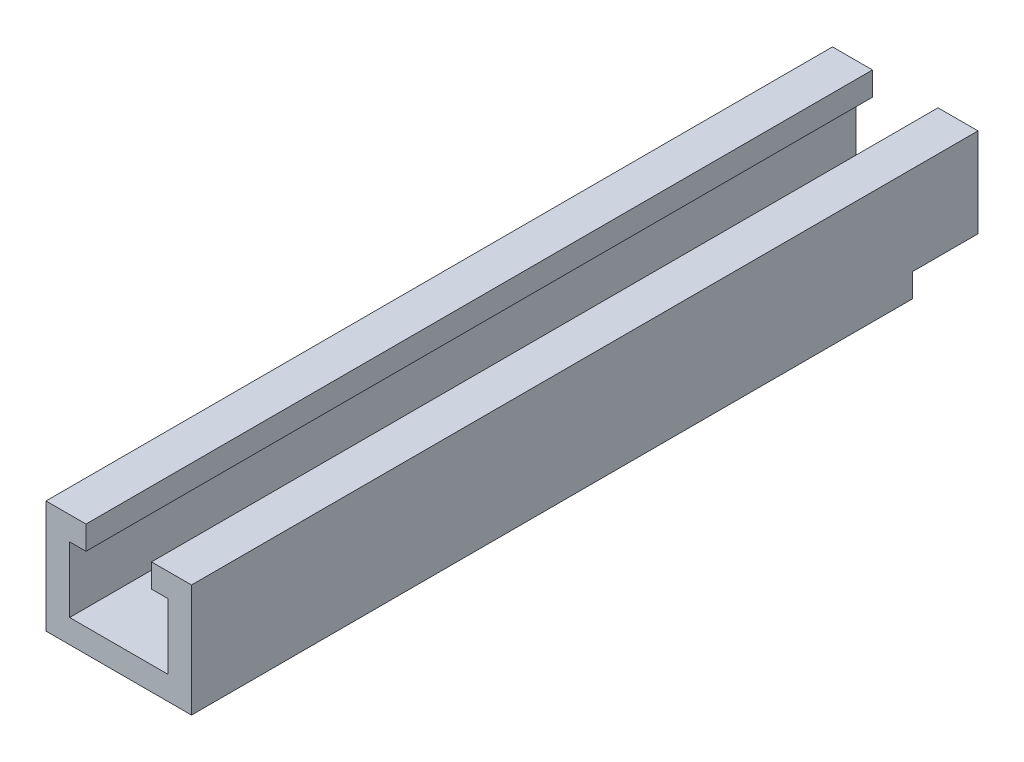
SolidWorks part; units mm, degrees
material "Beech"
ref_plane "Front Plane" through (0, 0, 0) normal (0, 0, 1) x (1, 0, 0)
ref_plane "Top Plane" through (0, 0, 0) normal (0, 1, 0) x (1, 0, 0)
ref_plane "Right Plane" through (0, 0, 0) normal (1, 0, 0) x (0, 0, -1)
sketch "Sketch1" plane through (0, 0, 0) normal (0, 0, 1) x (1, 0, 0)
  line L1 (0, 0) -> (111, 0)
  line L2 (0, 0) -> (0, 18)
  line L3 (0, 18) -> (111, 18)
  line L4 (111, 0) -> (111, 18)
  dimension "D1" = 18
  dimension "D2" = 111
extrude "baseplate" add sketch "Sketch1" along normal blind 600
sketch "Sketch2" plane through (0, 18, 0) normal (0, 1, 0) x (1, 0, 0)
  line L0 (111, -600) -> (0, -600) construction
  line L1 (0, 0) -> (18, 0)
  line L2 (0, 0) -> (0, -600)
  line L3 (0, -600) -> (18, -600)
  line L4 (18, 0) -> (18, -600)
  dimension "D1" = 18
extrude "side_rail" add sketch "Sketch2" along normal blind 50
sketch "Sketch3" plane through (0, 68, 0) normal (0, 1, 0) x (1, 0, 0)
  line L0 (111, -600) -> (18, -600) construction
  line L1 (0, 0) -> (30.5, 0)
  line L2 (0, 0) -> (0, -600)
  line L3 (0, -600) -> (30.5, -600)
  line L4 (30.5, 0) -> (30.5, -600)
  dimension "D1" = 30.5
extrude "keeper rail" add sketch "Sketch3" along normal blind 18
ref_plane "longitudinal midplane" through (55.5, 0, 0) normal (-1, 0, 0) x (0, 0, 1)
mirror "mirror rails" about plane through (55.5, 0, 0) normal (-1, 0, 0) of "keeper rail", "side_rail"
sketch "Sketch5" plane through (0, 0, 0) normal (0, -1, 0) x (1, 0, 0)
  line L0 (111, 600) -> (111, 0) construction
  line L1 (0, 0) -> (111, 0)
  line L2 (0, 0) -> (0, 50)
  line L3 (0, 50) -> (111, 50)
  line L4 (111, 0) -> (111, 50)
  dimension "D1" = 50
extrude "lap joint cutout" cut sketch "Sketch5" against normal blind 18
hole_wizard "lap joint bolt hole pattern" positions "Sketch7" profile "Sketch9" tap size "M5x0.8" standard "ANSI Metric"
sketch "Sketch7" plane through (0, 18, 0) normal (0, -1, 0) x (-1, 0, 0)
  line L1 (-102, -10) -> (-9, -10)
  line L2 (-102, -10) -> (-102, -40)
  line L3 (-102, -40) -> (-9, -40)
  line L4 (-9, -10) -> (-9, -40)
  line L5 (-102, 0) -> (-102, -10)
  line L6 (-93, 0) -> (-111, 0) construction
  line L8 (-9, -10) -> (-9, 0)
  line L9 (0, 0) -> (-18, 0) construction
  line L10 (-9, -25) -> (0, -25)
  line L11 (0, -50) -> (0, 0) construction
  point P1 (-102, -10)
  point P2 (-9, -40)
  point P113 (-102, -40)
  point P114 (-9, -10)
sketch "Sketch9" plane through (102, 18, 10) normal (1, 0, 0) x (0, 0, -1)
  line L0 (0, 0) -> (0, 15.2618)
  line L1 (0, 15.2618) -> (2.1, 14)
  line L2 (2.1, 14) -> (2.1, 0)
  line L5 (2.1, 0) -> (0, 0)
  line L10 (0, 15.2618) -> (-2.1, 14) construction
  line L11 (0, -6.35) -> (0, 107.95) construction
  dimension "Tap Drill Dia." = 4.2
  dimension "Tap Drill Depth" = 14
  dimension "Drill Angle" = 118
cosmetic thread "Hole Thread1" parameters "D1"=10, "D2"=5
cosmetic thread "Hole Thread2" parameters "D1"=10, "D2"=5
cosmetic thread "Hole Thread3" parameters "D1"=10, "D2"=5
cosmetic thread "Hole Thread4" parameters "D1"=10, "D2"=5
equation "\"board_thickness\" = 18mm"
equation "\"way_width\"= 75mm"
equation "\"way_thickness\"= 50mm"
equation "\"radial_clearance\"= 0.1mm"
equation "\"slider_width\"= \"way_width\"-2* \"radial_clearance\""
equation "\"slider_thickness\" = \"way_thickness\" - 2 * \"radial_clearance\""
equation "\"column_width\"= \"way_width\" + 2 * \"board_thickness\""
equation "\"D1@Sketch1\"=\"board_thickness\""
equation "\"D2@Sketch1\"=\"column_width\""
equation "\"D1@Sketch2\"=\"board_thickness\""
equation "\"D1@keeper rail\"=\"board_thickness\""
equation "\"boxway_slot_width\" = 50mm"
equation "\"keeper_rail_width\" = (\"column_width\" - \"boxway_slot_width\")/2"
equation "\"D1@Sketch3\"=\"keeper_rail_width\""
equation "\"slider_length\" = 125mm"
equation "\"nut_diameter\"= 22mm"
equation "\"nut_length\"= 15mm"
equation "\"leadscrew_diameter\"= 10mm"
equation "\"leadscrew_radial_clearance\"= 1mm"
equation "\"bearing_bolt_pattern_width\" = 35mm"
equation "\"bearing_bolt_pattern_height\" = 60mm"
equation "\"desktop_bolt_pattern_width\" = 30mm"
equation "\"desktop_bolt_pattern_height\" = 30mm"
equation "\"bearing_bolt_nut_counterbore_diameter\" = 12mm"
equation "\"bearing_bolt_nut_counterbore_depth\"= 10mm"
equation "\"desktop_depth\"= 500mm"
equation "\"desktop_width\"= 650mm"
equation "\"desktop_thickness\"= 15mm"
equation "\"leg_height\"=100mm"
equation "\"leg_width\"=18mm"
equation "\"leg_length\"=500mm"
equation "\"D1@lap joint cutout\" = \"leg_width\""
equation "\"lap_joint_height\" = 50mm"
equation "\"lap_dowel_diameter\"= 8mm"
equation "\"lap_dowel_hole_z_spacing\"=30"
equation "\"D1@Sketch5\"=\"lap_joint_height\""
equation "\"D1@Sketch7\"=\"lap_dowel_hole_z_spacing\""
